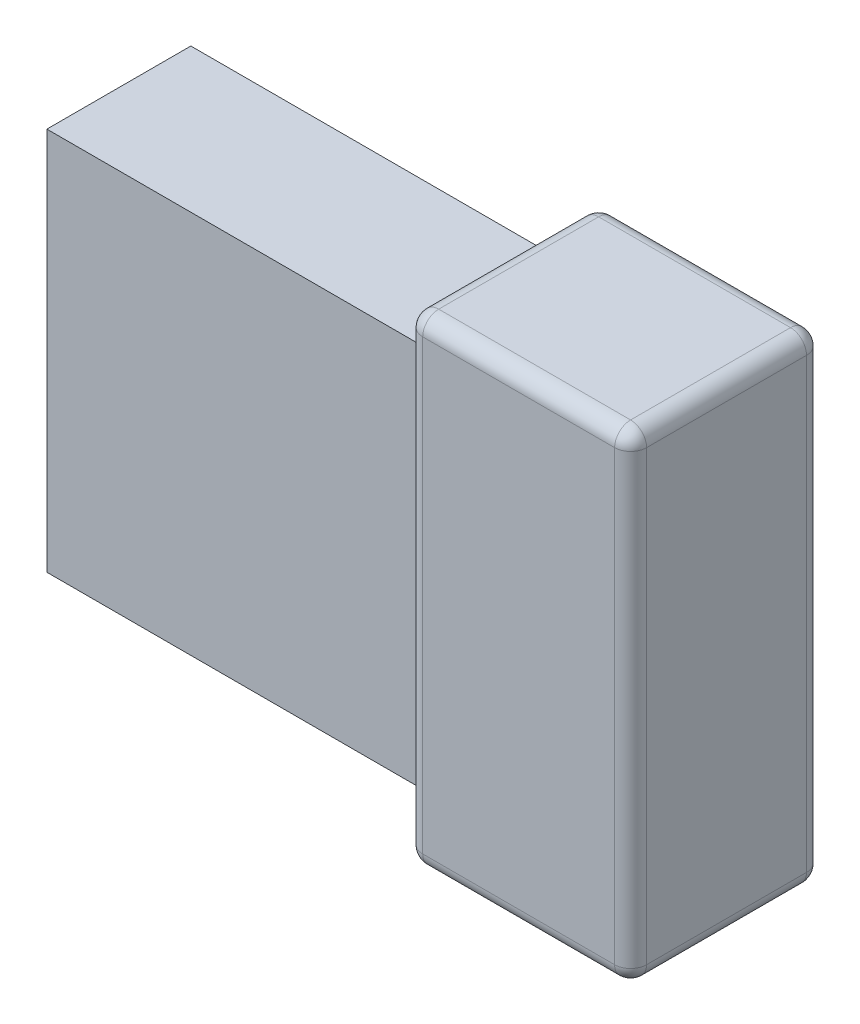
SolidWorks part; units mm, degrees
ref_plane "Front Plane" through (0, 0, 0) normal (0, 0, 1) x (1, 0, 0)
ref_plane "Top Plane" through (0, 0, 0) normal (0, 1, 0) x (1, 0, 0)
ref_plane "Right Plane" through (0, 0, 0) normal (1, 0, 0) x (0, 0, -1)
sketch "Sketch1" plane through (0, 0, 0) normal (0, 0, 1) x (1, 0, 0)
  line L0 (13, -7.5) -> (6, -7.5)
  line L1 (-6, -6) -> (6, -6)
  line L2 (-6, -6) -> (-6, 6)
  line L3 (-6, 6) -> (6, 6)
  line L4 (6, -6) -> (6, 6)
  line L5 (-6, -6) -> (6, 6) construction
  line L6 (-6, 6) -> (6, -6) construction
  line L7 (13, -7.5) -> (13, 7.5)
  line L8 (6, -7.5) -> (6, 7.5)
  line L9 (13, 7.5) -> (6, 7.5)
  line L10 (13, -7.5) -> (6, 7.5) construction
  line L11 (6, -7.5) -> (13, 7.5) construction
  point P0 (0, 0)
  point P7 (9.5, 0)
  dimension "D1" = 12
  dimension "D2" = 12
  dimension "D3" = 7
  dimension "D4" = 15
extrude "Boss-Extrude1" add sketch "Sketch1" along normal mid plane 4.5 contours L1 L4 L3 L2 region at (0, 0, 0)
extrude "Boss-Extrude2" add sketch "Sketch1<3>" along normal mid plane 6 contours L9 L8 L0 L7
sketch "Sketch1<3>" plane through (0, 0, 0) normal (0, 0, 1) x (1, 0, 0) same geometry as "Sketch1"
fillet "Fillet1" radius 0.5 12 edges at (6, 0, 3) (13, 0, 3) (6, -7.5, 0) (9.5, -7.5, 3) (13, -7.5, 0) (6, 0, -3) (9.5, -7.5, -3) (13, 0, -3) (13, 7.5, 0) (9.5, 7.5, 3) (6, 7.5, 0) (9.5, 7.5, -3)
other "Freeze***"
